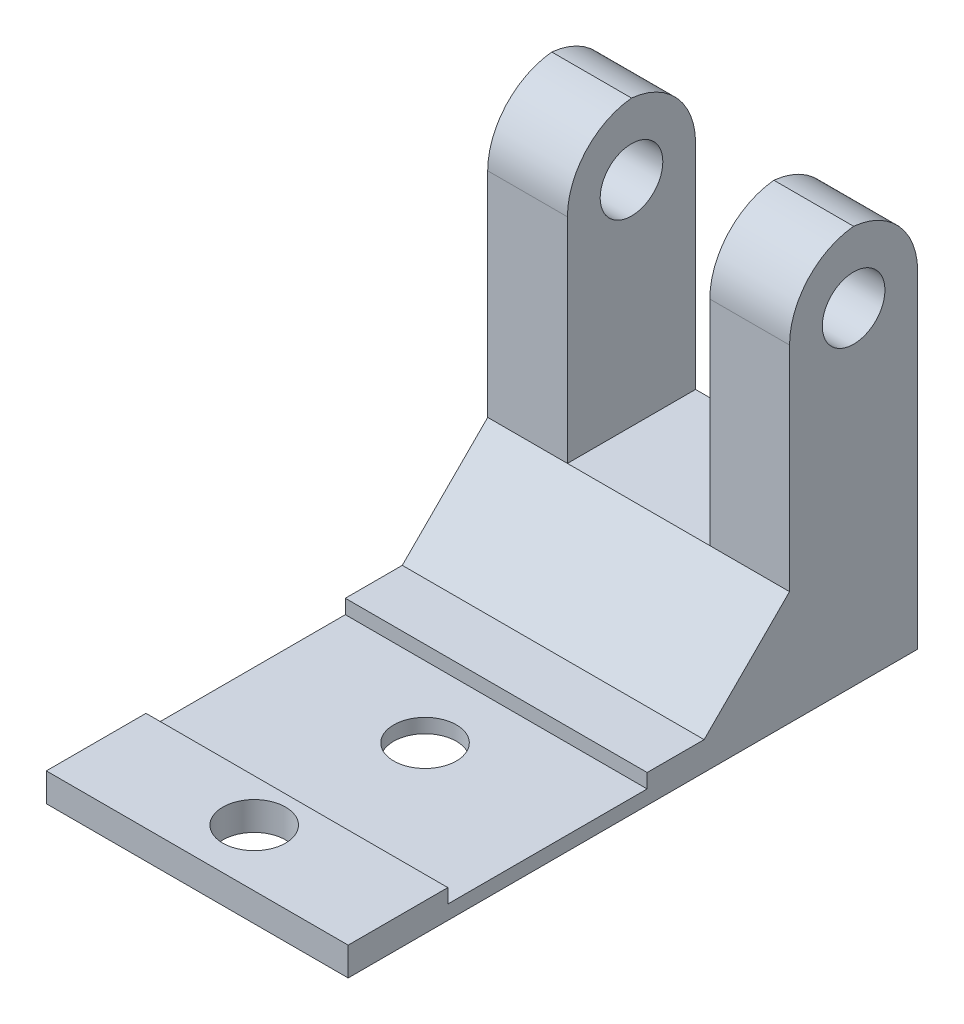
SolidWorks part; units mm, degrees
ref_plane "Ön Düzlem" through (0, 0, 0) normal (0, 0, 1) x (1, 0, 0)
ref_plane "Üst Düzlem" through (0, 0, 0) normal (0, 1, 0) x (1, 0, 0)
ref_plane "Sağ Düzlem" through (0, 0, 0) normal (1, 0, 0) x (0, 0, -1)
sketch "Sketch1" plane through (0, 0, 0) normal (0, 1, 0) x (1, 0, 0)
  line L0 (-14.28, 13.79) -> (-14.28, -6.21)
  line L1 (-14.28, -6.21) -> (-3.68, -6.21)
  line L2 (-3.68, -6.21) -> (-3.68, 13.79)
  line L3 (-3.68, 13.79) -> (-6.48, 13.79)
  line L4 (-6.48, 13.79) -> (-6.48, 8.79)
  line L5 (-6.48, 8.79) -> (-11.48, 8.79)
  line L6 (-11.48, 8.79) -> (-11.48, 13.79)
  line L7 (-11.48, 13.79) -> (-14.28, 13.79)
  circle A0 centre (-8.98, 4.79) radius 1.1
  circle A1 centre (-8.98, -1.21) radius 1.1
  dimension "D7" = 2.2
  dimension "D12" = 2.2
  dimension "D1" = 2.8
  dimension "D2" = 2.8
  dimension "D3" = 20
  dimension "D4" = 20
  dimension "D5" = 5
  dimension "D6" = 5
  dimension "D8" = 5.3
  dimension "D9" = 5.3
  dimension "D10" = 9
  dimension "D11" = 6
extrude "Boss-Extrude1" add sketch "Sketch1" along normal blind 1
sketch "Sketch2" plane through (0, 1, 0) normal (0, 1, 0) x (1, 0, 0)
  line L1 (-11.48, 8.79) -> (-14.28, 8.79)
  line L2 (-11.48, 8.79) -> (-11.48, 13.79)
  line L3 (-11.48, 13.79) -> (-14.28, 13.79)
  line L4 (-14.28, 8.79) -> (-14.28, 13.79)
  line L5 (-6.48, 8.79) -> (-3.68, 8.79)
  line L6 (-6.48, 8.79) -> (-6.48, 13.79)
  line L7 (-6.48, 13.79) -> (-3.68, 13.79)
  line L8 (-3.68, 8.79) -> (-3.68, 13.79)
extrude "Boss-Extrude2" add sketch "Sketch2" along normal blind 8
sketch "Sketch4" plane through (0, 0, -13.79) normal (0, 0, -1) x (-1, 0, 0)
  line L1 (3.68, 9) -> (6.48, 9)
  line L2 (3.68, 9) -> (3.68, 0)
  line L3 (3.68, 0) -> (6.48, 0)
  line L4 (6.48, 9) -> (6.48, 0)
  line L5 (11.48, 9) -> (14.28, 9)
  line L6 (11.48, 9) -> (11.48, 0)
  line L7 (11.48, 0) -> (14.28, 0)
  line L8 (14.28, 9) -> (14.28, 0)
extrude "Boss-Extrude3" add sketch "Sketch4" along normal blind 3
sketch "Sketch5" plane through (-3.68, 0, 0) normal (1, 0, 0) x (0, 0, -1)
  line L0 (16.79, 9) -> (16.79, 0) construction
  line L1 (8.79, 9) -> (16.79, 9) construction
  circle A0 centre (14.29, 7.5) radius 1.1
  dimension "D1" = 2.5
  dimension "D2" = 1.5
extrude "Cut-Extrude2" cut sketch "Sketch5" against normal blind 100
sketch "Sketch6" plane through (0, 9, 0) normal (0, 1, 0) x (1, 0, 0)
  line L1 (-11.48, 8.79) -> (-14.28, 8.79)
  line L2 (-11.48, 8.79) -> (-11.48, 16.79)
  line L3 (-11.48, 16.79) -> (-14.28, 16.79)
  line L4 (-14.28, 8.79) -> (-14.28, 16.79)
  line L5 (-6.48, 8.79) -> (-3.68, 8.79)
  line L6 (-6.48, 8.79) -> (-6.48, 16.79)
  line L7 (-6.48, 16.79) -> (-3.68, 16.79)
  line L8 (-3.68, 8.79) -> (-3.68, 16.79)
extrude "Boss-Extrude4" add sketch "Sketch6" along normal blind 1
sketch "Sketch7" plane through (-3.68, 0, 0) normal (1, 0, 0) x (0, 0, -1)
  line L0 (8.79, 10) -> (16.79, 10) construction
  line L1 (8.79, 1) -> (12.29, 1)
  line L2 (8.79, 1) -> (8.79, 10)
  line L3 (8.79, 10) -> (12.29, 10)
  line L4 (12.29, 1) -> (12.29, 10)
  dimension "D1" = 3.5
extrude "Cut-Extrude3" cut sketch "Sketch7" against normal blind 100
chamfer "Chamfer2" distance 3 angle 45 2 edges at (-5.08, 1, -12.29) (-12.88, 1, -12.29)
sketch "Sketch8" plane through (0, 1, 0) normal (0, 1, 0) x (1, 0, 0)
  line L0 (-14.28, 9.29) -> (-14.28, -6.21) construction
  line L1 (-3.68, -6.21) -> (-14.28, -6.21)
  line L2 (-3.68, -6.21) -> (-3.68, -3.21)
  line L3 (-3.68, -3.21) -> (-14.28, -3.21)
  line L4 (-14.28, -6.21) -> (-14.28, -3.21)
  dimension "D1" = 3
extrude "Cut-Extrude4" cut sketch "Sketch8" against normal blind 10
sketch "Sketch9" plane through (-11.48, 0, 0) normal (1, 0, 0) x (0, 0, -1)
  line L0 (8.79, 1) -> (9.29, 1)
  line L1 (9.29, 1) -> (12.29, 4)
  line L2 (12.29, 4) -> (16.79, 4)
  line L3 (16.79, 10) -> (16.79, 0) construction
  line L4 (16.79, 4) -> (16.79, 0)
  line L5 (16.79, 0) -> (8.79, 0)
  line L6 (8.79, 0) -> (8.79, 1)
extrude "Boss-Extrude5" add sketch "Sketch9" along normal up to surface (7.8 mm away) up to face at (-3.68, 7.5, -15.39)
sketch "Sketch10" plane through (0, 1, 0) normal (0, 1, 0) x (1, 0, 0)
  line L0 (-14.28, 9.29) -> (-14.28, -3.21) construction
  line L1 (-14.28, 0.29) -> (-3.68, 0.29)
  line L2 (-14.28, 0.29) -> (-14.28, 7.29)
  line L3 (-14.28, 7.29) -> (-3.68, 7.29)
  line L4 (-3.68, 0.29) -> (-3.68, 7.29)
  line L5 (-3.68, -3.21) -> (-3.68, 9.29) construction
  dimension "D1" = 2
  dimension "D2" = 3.5
extrude "Cut-Extrude5" cut sketch "Sketch10" against normal blind 0.5
sketch "Sketch11" plane through (0, 10, 0) normal (0, 1, 0) x (1, 0, 0)
  line L1 (-14.28, 16.79) -> (-11.48, 16.79)
  line L2 (-14.28, 16.79) -> (-14.28, 12.29)
  line L3 (-14.28, 12.29) -> (-11.48, 12.29)
  line L4 (-11.48, 16.79) -> (-11.48, 12.29)
  line L5 (-6.48, 12.29) -> (-3.68, 12.29)
  line L6 (-6.48, 12.29) -> (-6.48, 16.79)
  line L7 (-6.48, 16.79) -> (-3.68, 16.79)
  line L8 (-3.68, 12.29) -> (-3.68, 16.79)
extrude "Boss-Extrude6" add sketch "Sketch11" along normal blind 4
sketch "Sketch12" plane through (-3.68, 0, 0) normal (1, 0, 0) x (0, 0, -1)
  circle A0 centre (14.29, 7.5) radius 1.1
extrude "Boss-Extrude7" add sketch "Sketch12" against normal up to surface (10.6 mm away) up to face at (-14.28, 7.5, -15.39)
sketch "Sketch13" plane through (0, 14, 0) normal (0, 1, 0) x (1, 0, 0)
  line L1 (-11.48, 12.29) -> (-6.48, 12.29)
  line L2 (-11.48, 12.29) -> (-11.48, 16.79)
  line L3 (-11.48, 16.79) -> (-6.48, 16.79)
  line L4 (-6.48, 12.29) -> (-6.48, 16.79)
extrude "Cut-Extrude6" cut sketch "Sketch13" against normal up to surface (10 mm away) up to face at (-8.98, 4, -14.54)
sketch "Sketch14" plane through (-3.68, 0, 0) normal (1, 0, 0) x (0, 0, -1)
  line L0 (16.79, 14) -> (16.79, 0) construction
  line L3 (16.79, 14) -> (12.29, 14) construction
  circle A0 centre (14.54, 11.5) radius 1.1
  point P4 (14.54, 14)
  point P6 (14.5113, 14)
  dimension "D1" = 2.25
  dimension "D2" = 2.5
extrude "Cut-Extrude7" cut sketch "Sketch14" against normal blind 20
fillet "Fillet1" radius 2.5 4 edges at (-12.88, 14, -16.79) (-12.88, 14, -12.29) (-5.08, 14, -12.29) (-5.08, 14, -16.79)
